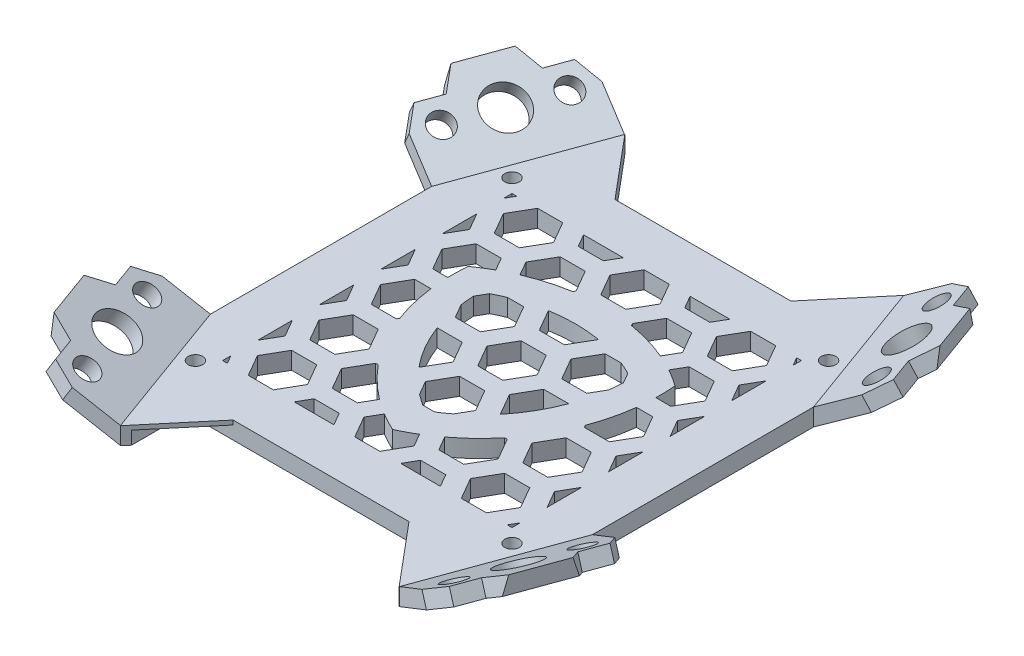
SolidWorks part; units mm, degrees
ref_plane "Front Plane" through (0, 0, 0) normal (0, 0, 1) x (1, 0, 0)
ref_plane "Top Plane" through (0, 0, 0) normal (0, 1, 0) x (1, 0, 0)
ref_plane "Right Plane" through (0, 0, 0) normal (1, 0, 0) x (0, 0, -1)
sketch "Sketch11" plane through (0, 0, 0) normal (0, 1, 0) x (1, 0, 0)
  line L0 (-50, -50) -> (-50, 50)
  line L1 (-30.4059, -66) -> (30.4059, -66)
  line L2 (-66, -38.2239) -> (-66, 0)
  line L3 (-30.4059, 66) -> (30.4059, 66)
  line L4 (66, -38.2239) -> (66, 38.2239)
  line L5 (-66, -66) -> (66, 66) construction
  line L6 (-50, 50) -> (66, -66) construction
  line L7 (-50, 50) -> (50, 50)
  line L8 (50, -50) -> (50, 50)
  line L9 (-50, -50) -> (50, -50)
  line L18 (-66, 0) -> (-66, 38.2239) construction
  line L19 (-66, -66) -> (-66, 66) construction
  line L20 (66, 38.2239) -> (66, 66) construction
  line L21 (66, -66) -> (66, 66) construction
  line L22 (66, -66) -> (66, -38.2239) construction
  line L23 (-66, -66) -> (-66, -38.2239) construction
  line L24 (-48.1804, 87.1828) -> (-65.9654, 38.3188)
  line L27 (-48.1804, 87.1828) -> (-30.4059, 66)
  line L28 (-66, 38.2239) -> (-66, 66) construction
  line L29 (-66, 66) -> (66, 66) construction
  line L30 (0, -55) -> (0, 55) construction
  line L31 (48.1804, 87.1828) -> (30.4059, 66)
  line L32 (65.9654, 38.3188) -> (66, 38.2239)
  line L33 (48.1804, 87.1828) -> (65.9654, 38.3188)
  line L34 (-55, 0) -> (55, 0) construction
  line L35 (65.9654, -38.3188) -> (66, -38.2239)
  line L36 (48.1804, -87.1828) -> (65.9654, -38.3188)
  line L37 (48.1804, -87.1828) -> (30.4059, -66)
  line L38 (-48.1804, -87.1828) -> (-30.4059, -66)
  line L39 (-65.9654, -38.3188) -> (-66, -38.2239)
  line L40 (-48.1804, -87.1828) -> (-65.9654, -38.3188)
  line L41 (30.4059, 66) -> (66, 66) construction
  line L42 (30.4059, -66) -> (66, -66) construction
  line L43 (-66, -66) -> (66, -66) construction
  line L44 (-66, -66) -> (-30.4059, -66) construction
  line L45 (-66, 66) -> (-30.4059, 66) construction
  line L46 (-57.0729, 62.7508) -> (-66, 66) construction
  line L47 (-66, 38.2239) -> (-66, 0)
  line L48 (-66, 38.2239) -> (-65.9654, 38.3188)
  point P0 (0, 0)
  dimension "D1" = 132
  dimension "D2" = 9.5
  dimension "D4" = 52
  dimension "D5" = 60
  dimension "D8" = 20
  dimension "D3" = 16
extrude "Boss-Extrude6" add sketch "Sketch11" along normal blind 6
ref_plane "Plane1" through (4.5644, 0, -12.5405) normal (0.342, 0, -0.9397) x (0, -1, 0)
sketch "Sketch12" plane through (4.5644, 0, -12.5405) normal (0.342, 0, -0.9397) x (0, -1, 0)
  line L0 (-6, 75.093) -> (-21, 101.0738)
  line L1 (-21, 101.0738) -> (-15, 101.0738)
  line L2 (-15, 101.0738) -> (0, 75.093)
  line L4 (-6, 75.093) -> (0, 75.093)
  dimension "D1" = 6
  dimension "D2" = 30
  dimension "D3" = 60
extrude "Boss-Extrude7" add sketch "Sketch12" along normal blind 52
sketch "Sketch13" plane through (-15.1997, -28.0162, -5.5322) normal (0.4698, 0.866, 0.171) x (0.8827, -0.4609, -0.091)
  line L0 (-51.2289, 92.4122) -> (-71.3763, 44.4738) construction
  line L1 (-65.0573, 98.2239) -> (-37.4005, 86.6004) construction
  line L2 (-85.2046, 50.2856) -> (-57.5479, 38.6621) construction
  line L3 (-65.0573, 98.2239) -> (-85.2046, 50.2856) construction
  line L5 (-71.7755, 82.2385) -> (-85.1655, 50.3787) construction
  line L6 (-78.4863, 66.2709) -> (-73.2618, 59.3889)
  line L15 (-73.2618, 59.3889) -> (-76.6247, 51.3873)
  line L16 (-76.6247, 51.3873) -> (-71.3763, 44.4738)
  line L17 (-51.2289, 92.4122) -> (-59.8399, 91.3237)
  line L24 (-71.7755, 82.2385) -> (-63.2027, 83.3222)
  line L25 (-63.2027, 83.3222) -> (-59.8399, 91.3237)
  line L37 (-71.3763, 44.4738) -> (-85.2046, 50.2856)
  line L38 (-85.2046, 50.2856) -> (-78.4863, 66.2709)
  line L39 (-71.7755, 82.2385) -> (-65.0573, 98.2239)
  line L40 (-65.0573, 98.2239) -> (-51.2289, 92.4122)
  line L41 (-85.1655, 50.3787) -> (-78.4863, 66.2709) construction
  line L49 (-44.1188, 70.6151) -> (-49.3553, 77.5128) [skipped]
  line L51 (-60.0486, 83.7209) -> (-71.7755, 82.2385) [skipped]
  line L52 (-81.8532, 58.3033) -> (-86.159, 57.7591) construction
  line L53 (-54.1654, 46.6668) -> (-56.7896, 50.1235) construction
  line L54 (-62.7648, 45.5623) -> (-61.0832, 49.5633) [skipped]
  line L55 (-71.3763, 44.4738) -> (-62.7648, 45.5623) [skipped]
  line L56 (-68.0134, 52.4754) -> (-62.5566, 53.1651) construction
  line L57 (-50.8296, 54.6474) -> (-44.1188, 70.6151) [skipped]
  circle A0 centre (-68.0132, 52.4758) radius 4
  circle A1 centre (-61.3026, 68.443) radius 7
  circle A2 centre (-54.592, 84.4101) radius 4
  dimension "D1" = 8
  dimension "D2" = 8
  dimension "D3" = 14
  dimension "D6" = 17.3397
  dimension "D4" = 17.32
  dimension "D5" = 17.32
  dimension "D7" = 17.3397
  dimension "D8" = 120
  dimension "D9" = 30
  dimension "D10" = 7.4833
  dimension "D11" = 30
extrude "Cut-Extrude1" cut sketch "Sketch13" against normal through all
mirror "Mirror3" about plane through (0, 0, 0) normal (1, 0, 0) of "Cut-Extrude1", "Boss-Extrude7"
mirror "Mirror4" about plane through (0, 0, 0) normal (0, 0, 1) of "Boss-Extrude7", "Cut-Extrude1", "Mirror3"
sketch "Sketch18" plane through (0, 0, 66) normal (0, 0, 1) x (1, 0, 0)
  line L0 (0, 6) -> (0, 0) construction
  line L1 (-30.4059, 6) -> (30.4059, 6) construction
  line L2 (-30.4059, 0) -> (30.4059, 0) construction
  line L3 (0, 4.5) -> (-46.4059, 4.5)
  line L4 (-46.4059, 4.5) -> (-46.4059, 0)
  line L6 (-46.4059, 0) -> (46.4059, 0)
  line L7 (30.4059, 0) -> (48.1804, 0) construction
  line L8 (46.4059, 0) -> (46.4059, 4.5)
  line L9 (46.4059, 4.5) -> (0, 4.5)
  line L11 (-30.4059, 6) -> (-30.4059, 0) construction
  line L12 (30.4059, 6) -> (30.4059, 0) construction
  line L13 (-48.1804, 0) -> (-30.4059, 0) construction
  dimension "D1" = 16
  dimension "D2" = 16
  dimension "D3" = 1.5
extrude "Cut-Extrude2" cut sketch "Sketch18" along normal through all
sketch "Sketch19" plane through (0, 6, 0) normal (0, 1, 0) x (1, 0, 0)
  line L0 (30.4059, 66) -> (-30.4059, 66) construction
  line L3 (-66, 38.2239) -> (-66, -38.2239) construction
  line L4 (66, -38.2239) -> (66, 38.2239) construction
  circle A0 centre (-54.7, 54.7) radius 2.5
  circle A1 centre (54.7, 54.7) radius 2.5
  circle A2 centre (54.7, -54.7) radius 2.5
  circle A3 centre (-54.7, -54.7) radius 2.5
  point P15 (0, 0)
  dimension "D1" = 5
  dimension "D2" = 11.3
  dimension "D3" = 11.3
  dimension "D5" = 11.3
  dimension "D6" = 11.3
  dimension "D4" = 4
extrude "Cut-Extrude3" cut sketch "Sketch19" against normal through all
sketch "Sketch20" plane through (0, 0, 0) normal (0, 1, 0) x (1, 0, 0)
  line L0 (0, 0) -> (0, -28.75) construction
  line L1 (0, 0) -> (-25.9808, 15) construction
  line L2 (0, 0) -> (24.8982, 14.375) construction
  line L3 (8.6603, 21.25) -> (4.3301, 28.75) construction
  line L4 (8.6603, 0) -> (4.3301, 7.5)
  line L5 (4.3301, 7.5) -> (-4.3301, 7.5)
  line L6 (-4.3301, 7.5) -> (-8.6603, 0)
  line L7 (-8.6603, 0) -> (-4.3301, -7.5)
  line L8 (-4.3301, -7.5) -> (4.3301, -7.5)
  line L9 (4.3301, -7.5) -> (8.6603, 0)
  line L10 (4.3301, 28.75) -> (-4.3301, 28.75) construction
  line L11 (-4.3301, 28.75) -> (-8.6603, 21.25) construction
  line L12 (-8.6522, 21.2361) -> (-4.3301, 13.75)
  line L13 (-4.3301, 13.75) -> (4.3301, 13.75)
  line L14 (4.3301, 13.75) -> (8.6522, 21.2361)
  line L15 (8.6603, 42.5) -> (4.3301, 50)
  line L16 (4.3301, 50) -> (-4.3301, 50)
  line L17 (-4.3301, 50) -> (-8.6603, 42.5)
  line L18 (-8.6603, 42.5) -> (-4.3301, 35)
  line L19 (-4.3301, 35) -> (4.3301, 35)
  line L20 (4.3301, 35) -> (8.6603, 42.5)
  line L21 (-11.55, 0) -> (11.55, 0) construction
  line L22 (4.3301, -13.75) -> (8.6603, -21.25)
  line L23 (-4.3301, -13.75) -> (4.3301, -13.75)
  line L24 (-8.6603, -21.25) -> (-4.3301, -13.75)
  line L25 (-5.899, -26.0327) -> (-8.6603, -21.25)
  line L26 (2.0538, -28.75) -> (-2.0538, -28.75)
  line L27 (8.6603, -21.25) -> (5.899, -26.0327)
  line L28 (6.0762, -38.0243) -> (8.6603, -42.5)
  line L29 (-4.3301, -35) -> (4.3301, -35) construction
  line L30 (-8.6603, -42.5) -> (-6.0762, -38.0243)
  line L31 (-4.3301, -50) -> (-8.6603, -42.5)
  line L32 (4.3301, -50) -> (-4.3301, -50)
  line L33 (8.6603, -42.5) -> (4.3301, -50)
  line L34 (4.3301, -7.5) -> (4.3301, -13.75) construction
  line L35 (4.3301, -10.625) -> (18.403, -10.625) construction
  line L36 (11.2674, -34.5157) -> (14.0729, -39.375)
  line L37 (9.7428, -10.625) -> (14.0649, -18.1111)
  line L38 (18.403, -18.125) -> (22.7332, -18.125) construction
  line L39 (22.7332, -18.125) -> (24.8982, -14.375) construction
  line L40 (24.8982, -6.875) -> (22.7332, -3.125) construction
  line L41 (22.7171, -3.125) -> (14.0729, -3.125)
  line L42 (14.0729, -3.125) -> (9.7428, -10.625)
  line L43 (14.0729, -39.375) -> (22.7332, -39.375)
  line L44 (22.7332, -39.375) -> (27.0633, -31.875)
  line L45 (27.0633, -31.875) -> (22.7332, -24.375)
  line L46 (22.7332, -24.375) -> (21.8611, -24.375)
  line L47 (14.0729, -24.375) -> (9.7428, -31.875) construction
  line L48 (9.7428, -53.125) -> (14.0729, -60.625) construction
  line L49 (14.0729, -60.625) -> (22.7332, -60.625) construction
  line L50 (22.7332, -60.625) -> (27.0633, -53.125) construction
  line L51 (25.2591, -50) -> (22.7332, -45.625)
  line L52 (22.7332, -45.625) -> (14.0729, -45.625)
  line L53 (14.0729, -45.625) -> (11.547, -50)
  line L54 (14.0729, 45.625) -> (11.547, 50)
  line L55 (22.7332, 45.625) -> (14.0729, 45.625)
  line L56 (25.2591, 50) -> (22.7332, 45.625)
  line L57 (22.7332, 60.625) -> (27.0633, 53.125) construction
  line L58 (14.0729, 60.625) -> (22.7332, 60.625) construction
  line L59 (9.7428, 53.125) -> (14.0729, 60.625) construction
  line L60 (10.1788, 31.1197) -> (9.7428, 31.875)
  line L61 (22.7332, 24.375) -> (14.0729, 24.375) construction
  line L62 (27.0633, 31.875) -> (24.2578, 27.0157)
  line L63 (22.7332, 39.375) -> (27.0633, 31.875)
  line L64 (14.0729, 39.375) -> (22.7332, 39.375)
  line L65 (9.7428, 31.875) -> (14.0729, 39.375)
  line L66 (14.0729, 3.125) -> (9.7428, 10.625)
  line L67 (22.7332, 3.125) -> (14.0729, 3.125)
  line L68 (25.4945, 7.9077) -> (22.7332, 3.125)
  line L69 (23.8713, 16.1537) -> (25.9251, 12.5963)
  line L70 (14.0729, 18.125) -> (19.5955, 18.125)
  line L71 (9.7428, 10.625) -> (14.0729, 18.125)
  line L72 (45.4663, 42.5) -> (41.1362, 50)
  line L73 (41.1362, 50) -> (32.476, 50)
  line L74 (32.476, 50) -> (28.1458, 42.5)
  line L75 (28.1458, 42.5) -> (32.476, 35)
  line L76 (32.476, 35) -> (41.1362, 35)
  line L77 (41.1362, 35) -> (45.4663, 42.5)
  line L78 (50, 47.1475) -> (48.3531, 50)
  line L79 (46.5489, 53.125) -> (50.879, 60.625) construction
  line L80 (50.879, 60.625) -> (59.5392, 60.625) construction
  line L81 (59.5392, 60.625) -> (63.8694, 53.125) construction
  line L82 (63.8694, 53.125) -> (59.5392, 45.625) construction
  line L83 (59.5392, 45.625) -> (50.879, 45.625) construction
  line L84 (50, 25.8975) -> (46.5489, 31.875)
  line L85 (46.5489, 31.875) -> (50, 37.8525)
  line L86 (50.879, 39.375) -> (59.5392, 39.375) construction
  line L87 (59.5392, 39.375) -> (63.8694, 31.875) construction
  line L88 (63.8694, 31.875) -> (59.5392, 24.375) construction
  line L89 (59.5392, 24.375) -> (50.879, 24.375) construction
  line L90 (45.4663, 21.25) -> (41.1362, 28.75)
  line L91 (41.1362, 28.75) -> (32.476, 28.75)
  line L92 (32.476, 28.75) -> (29.8919, 24.2743)
  line L93 (28.1458, 21.25) -> (32.476, 13.75) construction
  line L94 (35.9682, 13.75) -> (41.1362, 13.75)
  line L95 (41.1362, 13.75) -> (45.4663, 21.25)
  line L96 (50, 4.6475) -> (46.5489, 10.625)
  line L97 (46.5489, 10.625) -> (50, 16.6025)
  line L98 (50.879, 18.125) -> (59.5392, 18.125) construction
  line L99 (59.5392, 18.125) -> (63.8694, 10.625) construction
  line L100 (63.8694, 10.625) -> (59.5392, 3.125) construction
  line L101 (59.5392, 3.125) -> (50.879, 3.125) construction
  line L102 (45.4663, 0) -> (41.1362, 7.5)
  line L103 (41.1362, 7.5) -> (35.5252, 7.5)
  line L104 (32.476, 7.5) -> (28.1458, 0) construction
  line L105 (32.0399, -6.7447) -> (32.476, -7.5)
  line L106 (32.476, -7.5) -> (41.1362, -7.5)
  line L107 (41.1362, -7.5) -> (45.4663, 0)
  line L108 (41.1362, -13.75) -> (45.4663, -21.25)
  line L109 (45.4663, -21.25) -> (41.1362, -28.75)
  line L110 (41.1362, -28.75) -> (32.476, -28.75)
  line L111 (32.476, -28.75) -> (28.1458, -21.25)
  line L112 (28.1458, -21.25) -> (32.476, -13.75)
  line L113 (32.476, -13.75) -> (41.1362, -13.75)
  line L114 (46.5489, -10.625) -> (50, -16.6025)
  line L115 (50.879, -18.125) -> (59.5392, -18.125) construction
  line L116 (59.5392, -18.125) -> (63.8694, -10.625) construction
  line L117 (63.8694, -10.625) -> (59.5392, -3.125) construction
  line L118 (59.5392, -3.125) -> (50.879, -3.125) construction
  line L119 (50, -4.6475) -> (46.5489, -10.625)
  line L120 (46.5489, -31.875) -> (50, -37.8525)
  line L121 (50.879, -39.375) -> (59.5392, -39.375) construction
  line L122 (59.5392, -39.375) -> (63.8694, -31.875) construction
  line L123 (63.8694, -31.875) -> (59.5392, -24.375) construction
  line L124 (59.5392, -24.375) -> (50.879, -24.375) construction
  line L125 (50, -25.8975) -> (46.5489, -31.875)
  line L126 (41.1362, -35) -> (45.4663, -42.5)
  line L127 (45.4663, -42.5) -> (41.1362, -50)
  line L128 (41.1362, -50) -> (32.476, -50)
  line L129 (32.476, -50) -> (28.1458, -42.5)
  line L130 (28.1458, -42.5) -> (32.476, -35)
  line L131 (32.476, -35) -> (41.1362, -35)
  line L132 (46.5489, -53.125) -> (50.879, -60.625) construction
  line L133 (50.879, -60.625) -> (59.5392, -60.625) construction
  line L134 (59.5392, -60.625) -> (63.8694, -53.125) construction
  line L135 (63.8694, -53.125) -> (59.5392, -45.625) construction
  line L136 (59.5392, -45.625) -> (50.879, -45.625) construction
  line L137 (50, -47.1475) -> (48.3531, -50)
  line L138 (0, -11.55) -> (0, 11.55) construction
  line L139 (-50, -47.1475) -> (-48.3531, -50)
  line L140 (-59.5392, -45.625) -> (-50.879, -45.625) construction
  line L141 (-63.8694, -53.125) -> (-59.5392, -45.625) construction
  line L142 (-59.5392, -60.625) -> (-63.8694, -53.125) construction
  line L143 (-50.879, -60.625) -> (-59.5392, -60.625) construction
  line L144 (-46.5489, -53.125) -> (-50.879, -60.625) construction
  line L145 (-50, -25.8975) -> (-46.5489, -31.875)
  line L146 (-59.5392, -24.375) -> (-50.879, -24.375) construction
  line L147 (-63.8694, -31.875) -> (-59.5392, -24.375) construction
  line L148 (-59.5392, -39.375) -> (-63.8694, -31.875) construction
  line L149 (-50.879, -39.375) -> (-59.5392, -39.375) construction
  line L150 (-46.5489, -31.875) -> (-50, -37.8525)
  line L151 (-50, -4.6475) -> (-46.5489, -10.625)
  line L152 (-59.5392, -3.125) -> (-50.879, -3.125) construction
  line L153 (-63.8694, -10.625) -> (-59.5392, -3.125) construction
  line L154 (-59.5392, -18.125) -> (-63.8694, -10.625) construction
  line L155 (-50.879, -18.125) -> (-59.5392, -18.125) construction
  line L156 (-46.5489, -10.625) -> (-50, -16.6025)
  line L157 (-59.5392, 3.125) -> (-50.879, 3.125) construction
  line L158 (-63.8694, 10.625) -> (-59.5392, 3.125) construction
  line L159 (-59.5392, 18.125) -> (-63.8694, 10.625) construction
  line L160 (-50.879, 18.125) -> (-59.5392, 18.125) construction
  line L161 (-46.5489, 10.625) -> (-50, 16.6025)
  line L162 (-50, 4.6475) -> (-46.5489, 10.625)
  line L163 (-59.5392, 24.375) -> (-50.879, 24.375) construction
  line L164 (-63.8694, 31.875) -> (-59.5392, 24.375) construction
  line L165 (-59.5392, 39.375) -> (-63.8694, 31.875) construction
  line L166 (-50.879, 39.375) -> (-59.5392, 39.375) construction
  line L167 (-46.5489, 31.875) -> (-50, 37.8525)
  line L168 (-50, 25.8975) -> (-46.5489, 31.875)
  line L169 (-59.5392, 45.625) -> (-50.879, 45.625) construction
  line L170 (-63.8694, 53.125) -> (-59.5392, 45.625) construction
  line L171 (-59.5392, 60.625) -> (-63.8694, 53.125) construction
  line L172 (-50.879, 60.625) -> (-59.5392, 60.625) construction
  line L173 (-46.5489, 53.125) -> (-50.879, 60.625) construction
  line L174 (-50, 47.1475) -> (-48.3531, 50)
  line L175 (-41.1362, 35) -> (-45.4663, 42.5)
  line L176 (-32.476, 35) -> (-41.1362, 35)
  line L177 (-28.1458, 42.5) -> (-32.476, 35)
  line L178 (-32.476, 50) -> (-28.1458, 42.5)
  line L179 (-41.1362, 50) -> (-32.476, 50)
  line L180 (-45.4663, 42.5) -> (-41.1362, 50)
  line L181 (-41.1362, 13.75) -> (-45.4663, 21.25)
  line L182 (-35.9682, 13.75) -> (-41.1362, 13.75)
  line L183 (-28.1458, 21.25) -> (-32.476, 13.75) construction
  line L184 (-32.476, 28.75) -> (-29.8919, 24.2743)
  line L185 (-41.1362, 28.75) -> (-32.476, 28.75)
  line L186 (-45.4663, 21.25) -> (-41.1362, 28.75)
  line L187 (-41.1362, -7.5) -> (-45.4663, 0)
  line L188 (-32.476, -7.5) -> (-41.1362, -7.5)
  line L189 (-32.0399, -6.7447) -> (-32.476, -7.5)
  line L190 (-32.476, 7.5) -> (-28.1458, 0) construction
  line L191 (-41.1362, 7.5) -> (-35.5252, 7.5)
  line L192 (-45.4663, 0) -> (-41.1362, 7.5)
  line L193 (-32.476, -13.75) -> (-41.1362, -13.75)
  line L194 (-28.1458, -21.25) -> (-32.476, -13.75)
  line L195 (-32.476, -28.75) -> (-28.1458, -21.25)
  line L196 (-41.1362, -28.75) -> (-32.476, -28.75)
  line L197 (-45.4663, -21.25) -> (-41.1362, -28.75)
  line L198 (-41.1362, -13.75) -> (-45.4663, -21.25)
  line L199 (-32.476, -35) -> (-41.1362, -35)
  line L200 (-28.1458, -42.5) -> (-32.476, -35)
  line L201 (-32.476, -50) -> (-28.1458, -42.5)
  line L202 (-41.1362, -50) -> (-32.476, -50) construction
  line L203 (-45.4663, -42.5) -> (-41.1362, -50)
  line L204 (-41.1362, -35) -> (-45.4663, -42.5)
  line L205 (-14.0729, -45.625) -> (-11.547, -50)
  line L206 (-22.7332, -45.625) -> (-14.0729, -45.625)
  line L207 (-25.2591, -50) -> (-22.7332, -45.625)
  line L208 (-22.7332, -60.625) -> (-27.0633, -53.125) construction
  line L209 (-14.0729, -60.625) -> (-22.7332, -60.625) construction
  line L210 (-9.7428, -53.125) -> (-14.0729, -60.625) construction
  line L211 (-14.0729, -24.375) -> (-9.7428, -31.875) construction
  line L212 (-22.7332, -24.375) -> (-21.8611, -24.375)
  line L213 (-27.0633, -31.875) -> (-22.7332, -24.375)
  line L214 (-22.7332, -39.375) -> (-27.0633, -31.875)
  line L215 (-14.0729, -39.375) -> (-22.7332, -39.375)
  line L216 (-11.2674, -34.5157) -> (-14.0729, -39.375)
  line L217 (-14.0729, -3.125) -> (-9.7428, -10.625)
  line L218 (-22.7171, -3.125) -> (-14.0729, -3.125)
  line L219 (-27.0633, -10.625) -> (-22.7332, -3.125) construction
  line L220 (-22.7332, -18.125) -> (-27.0633, -10.625) construction
  line L221 (-14.0729, -18.125) -> (-22.7332, -18.125) construction
  line L222 (-9.7428, -10.625) -> (-14.0649, -18.1111)
  line L223 (-22.7332, 3.125) -> (-14.0729, 3.125)
  line L224 (-25.4945, 7.9077) -> (-22.7332, 3.125)
  line L225 (-23.8713, 16.1537) -> (-25.9251, 12.5963)
  line L226 (-14.0729, 18.125) -> (-19.5955, 18.125)
  line L227 (-9.7428, 10.625) -> (-14.0729, 18.125)
  line L228 (-14.0729, 3.125) -> (-9.7428, 10.625)
  line L229 (-22.7332, 24.375) -> (-14.0729, 24.375) construction
  line L230 (-27.0633, 31.875) -> (-24.2578, 27.0157)
  line L231 (-22.7332, 39.375) -> (-27.0633, 31.875)
  line L232 (-14.0729, 39.375) -> (-22.7332, 39.375)
  line L233 (-9.7428, 31.875) -> (-14.0729, 39.375)
  line L234 (-10.1788, 31.1197) -> (-9.7428, 31.875)
  line L235 (-22.7332, 45.625) -> (-14.0729, 45.625)
  line L236 (-25.2591, 50) -> (-22.7332, 45.625)
  line L237 (-22.7332, 60.625) -> (-27.0633, 53.125) construction
  line L238 (-14.0729, 60.625) -> (-22.7332, 60.625) construction
  line L239 (-9.7428, 53.125) -> (-14.0729, 60.625) construction
  line L240 (-14.0729, 45.625) -> (-11.547, 50)
  line L241 (-48.3531, 50) -> (-46.5489, 53.125) construction
  line L242 (-48.3531, 50) -> (-25.2591, 50)
  line L243 (-50, 47.1475) -> (-50, 37.8525)
  line L244 (-48.3531, -50) -> (-25.2591, -50) construction
  line L245 (50, 47.1475) -> (50, 37.8525)
  line L246 (-50.879, 45.625) -> (-50, 47.1475) construction
  line L247 (-50, 50) -> (-50, 47.1475) construction
  line L248 (-50, 50) -> (-48.3531, 50) construction
  line L249 (-50, 37.8525) -> (-50.879, 39.375) construction
  line L250 (-50.879, 24.375) -> (-50, 25.8975) construction
  line L251 (-50, 16.6025) -> (-50.879, 18.125) construction
  line L252 (-50.879, 3.125) -> (-50, 4.6475) construction
  line L253 (-50.879, -3.125) -> (-50, -4.6475) construction
  line L254 (-50, -16.6025) -> (-50.879, -18.125) construction
  line L255 (-50, 37.8525) -> (-50, 25.8975) construction
  line L256 (-50, 25.8975) -> (-50, 16.6025)
  line L257 (-50, 16.6025) -> (-50, 4.6475) construction
  line L258 (-50, 4.6475) -> (-50, -4.6475)
  line L259 (-50, -4.6475) -> (-50, -16.6025) construction
  line L260 (-50, -16.6025) -> (-50, -25.8975)
  line L261 (-50, -25.8975) -> (-50, -37.8525) construction
  line L262 (-50, -37.8525) -> (-50, -47.1475)
  line L263 (-50.879, -24.375) -> (-50, -25.8975) construction
  line L264 (-50, -37.8525) -> (-50.879, -39.375) construction
  line L265 (-50.879, -45.625) -> (-50, -47.1475) construction
  line L266 (-48.3531, -50) -> (-46.5489, -53.125) construction
  line L267 (-50, -50) -> (-48.3531, -50) construction
  line L268 (-50, -47.1475) -> (-50, -50) construction
  line L269 (-27.0633, -53.125) -> (-25.2591, -50) construction
  line L270 (-11.547, -50) -> (-9.7428, -53.125) construction
  line L271 (11.547, -50) -> (9.7428, -53.125) construction
  line L272 (27.0633, -53.125) -> (25.2591, -50) construction
  line L273 (11.547, -50) -> (25.2591, -50) construction
  line L274 (25.2591, -50) -> (48.3531, -50)
  line L275 (-25.2591, -50) -> (-11.547, -50) construction
  line L276 (-11.547, -50) -> (11.547, -50)
  line L277 (48.3531, -50) -> (46.5489, -53.125) construction
  line L278 (50.879, -45.625) -> (50, -47.1475) construction
  line L279 (50, -47.1475) -> (50, -50) construction
  line L280 (48.3531, -50) -> (50, -50) construction
  line L281 (50.879, -24.375) -> (50, -25.8975) construction
  line L282 (50, -37.8525) -> (50.879, -39.375) construction
  line L283 (50, -25.8975) -> (50, -37.8525) construction
  line L284 (50, -37.8525) -> (50, -47.1475)
  line L285 (50.879, -3.125) -> (50, -4.6475) construction
  line L286 (50, -16.6025) -> (50.879, -18.125) construction
  line L287 (50, -4.6475) -> (50, -16.6025) construction
  line L288 (50, -16.6025) -> (50, -25.8975)
  line L289 (50, 16.6025) -> (50.879, 18.125) construction
  line L290 (50.879, 3.125) -> (50, 4.6475) construction
  line L291 (50, 16.6025) -> (50, 4.6475) construction
  line L292 (50, 4.6475) -> (50, -4.6475)
  line L293 (50, 37.8525) -> (50.879, 39.375) construction
  line L294 (50.879, 24.375) -> (50, 25.8975) construction
  line L295 (50, 37.8525) -> (50, 25.8975) construction
  line L296 (50, 25.8975) -> (50, 16.6025)
  line L297 (50.879, 45.625) -> (50, 47.1475) construction
  line L298 (48.3531, 50) -> (46.5489, 53.125) construction
  line L299 (48.3531, 50) -> (50, 50) construction
  line L300 (50, 50) -> (50, 47.1475) construction
  line L301 (11.547, 50) -> (9.7428, 53.125) construction
  line L302 (27.0633, 53.125) -> (25.2591, 50) construction
  line L303 (11.547, 50) -> (25.2591, 50) construction
  line L304 (25.2591, 50) -> (48.3531, 50)
  line L305 (-11.547, 50) -> (-9.7428, 53.125) construction
  line L306 (-27.0633, 53.125) -> (-25.2591, 50) construction
  line L307 (-25.2591, 50) -> (-11.547, 50) construction
  line L308 (-11.547, 50) -> (11.547, 50)
  line L309 (-14.0729, 24.375) -> (-10.1788, 31.1197) construction
  line L310 (-24.2578, 27.0157) -> (-22.7332, 24.375) construction
  line L311 (14.0729, 24.375) -> (10.1788, 31.1197) construction
  line L312 (24.2578, 27.0157) -> (22.7332, 24.375) construction
  line L313 (29.8919, 24.2743) -> (28.1458, 21.25) construction
  line L314 (32.476, 13.75) -> (35.9682, 13.75) construction
  line L315 (35.5252, 7.5) -> (32.476, 7.5) construction
  line L316 (28.1458, 0) -> (32.0399, -6.7447) construction
  line L317 (21.8611, -24.375) -> (14.0729, -24.375) construction
  line L318 (9.7428, -31.875) -> (11.2674, -34.5157) construction
  line L319 (-6.0762, -38.0243) -> (-4.3301, -35) construction
  line L320 (4.3301, -35) -> (6.0762, -38.0243) construction
  line L321 (-21.8611, -24.375) -> (-14.0729, -24.375) construction
  line L322 (-9.7428, -31.875) -> (-11.2674, -34.5157) construction
  line L323 (-28.1458, 0) -> (-32.0399, -6.7447) construction
  line L324 (-35.5252, 7.5) -> (-32.476, 7.5) construction
  line L325 (-32.476, 13.75) -> (-35.9682, 13.75) construction
  line L326 (-29.8919, 24.2743) -> (-28.1458, 21.25) construction
  line L327 (-22.7332, 18.125) -> (-23.8713, 16.1537) construction
  line L328 (-19.5955, 18.125) -> (-22.7332, 18.125) construction
  line L329 (-25.9251, 12.5963) -> (-27.0633, 10.625) construction
  line L330 (-27.0633, 10.625) -> (-25.4945, 7.9077) construction
  line L331 (-4.3301, -28.75) -> (-5.899, -26.0327) construction
  line L332 (-2.0538, -28.75) -> (-4.3301, -28.75) construction
  line L333 (4.3301, -28.75) -> (2.0538, -28.75) construction
  line L334 (5.899, -26.0327) -> (4.3301, -28.75) construction
  line L335 (0, -28.75) -> (0, -30) construction
  line L336 (14.0729, -18.125) -> (18.403, -18.125) construction
  line L337 (27.0633, -10.625) -> (24.8982, -6.875) construction
  line L338 (24.8982, -14.375) -> (27.0633, -10.625) construction
  line L339 (25.9251, 12.5963) -> (27.0633, 10.625) construction
  line L340 (27.0633, 10.625) -> (25.4945, 7.9077) construction
  line L341 (24.8982, 14.375) -> (25.9808, 15) construction
  line L342 (22.7332, 18.125) -> (23.8713, 16.1537) construction
  line L343 (19.5955, 18.125) -> (22.7332, 18.125) construction
  line L344 (-8.6603, 21.25) -> (-8.6522, 21.2361) construction
  line L345 (8.6522, 21.2361) -> (8.6603, 21.25) construction
  line L346 (22.7332, -3.125) -> (22.7171, -3.125) construction
  line L347 (14.0649, -18.1111) -> (14.0729, -18.125) construction
  line L348 (-14.0649, -18.1111) -> (-14.0729, -18.125) construction
  line L349 (-22.7332, -3.125) -> (-22.7171, -3.125) construction
  line L350 (-41.1362, -50) -> (-48.3531, -50)
  line L351 (-32.476, -50) -> (-25.2591, -50)
  arc A0 (2.0538, -28.75) -> (5.899, -26.0327) centre (-25.9808, 15) ccw
  arc A1 (-25.9251, 12.5963) -> (-25.4945, 7.9077) centre (25.9808, 15) ccw
  arc A2 (23.8713, 16.1537) -> (19.5955, 18.125) centre (0, -30) ccw
  arc A3 (0, -41.2515) -> (6.0762, -38.0243) centre (-25.9808, 15) ccw
  arc A4 (35.7248, 20.6257) -> (29.8919, 24.2743) centre (0, -30) ccw
  arc A5 (-35.7248, 20.6257) -> (-35.9682, 13.75) centre (25.9808, 15) ccw
  circle A6 centre (0, 0) radius 7.5 construction
  arc A7 (18.403, -18.125) -> (24.8982, -14.375) centre (18.403, -10.625) ccw construction
  arc A8 (-24.2578, 27.0157) -> (-29.8919, 24.2743) centre (0, -30) ccw construction
  arc A9 (-29.8919, 24.2743) -> (-35.7248, 20.6257) centre (0, -30) ccw
  arc A10 (35.7248, 20.6257) -> (-35.7248, 20.6257) centre (0, -30) ccw construction
  arc A11 (10.1788, 31.1197) -> (-10.1788, 31.1197) centre (0, -30) ccw construction
  arc A12 (-10.1788, 31.1197) -> (-24.2578, 27.0157) centre (0, -30) ccw
  arc A13 (29.8919, 24.2743) -> (24.2578, 27.0157) centre (0, -30) ccw construction
  arc A14 (24.2578, 27.0157) -> (10.1788, 31.1197) centre (0, -30) ccw
  arc A15 (-8.6522, 21.2361) -> (-19.5955, 18.125) centre (0, -30) ccw construction
  arc A16 (-19.5955, 18.125) -> (-23.8713, 16.1537) centre (0, -30) ccw
  arc A17 (25.9808, 15) -> (-25.9808, 15) centre (0, -30) ccw construction
  arc A18 (19.5955, 18.125) -> (8.6522, 21.2361) centre (0, -30) ccw construction
  arc A19 (8.6522, 21.2361) -> (-8.6522, 21.2361) centre (0, -30) ccw
  arc A20 (35.5252, 7.5) -> (35.9682, 13.75) centre (-25.9808, 15) ccw construction
  arc A21 (35.9682, 13.75) -> (35.7248, 20.6257) centre (-25.9808, 15) ccw
  arc A22 (0, -41.2515) -> (35.7248, 20.6257) centre (-25.9808, 15) ccw construction
  arc A23 (21.8611, -24.375) -> (32.0399, -6.7447) centre (-25.9808, 15) ccw construction
  arc A24 (32.0399, -6.7447) -> (35.5252, 7.5) centre (-25.9808, 15) ccw
  arc A25 (6.0762, -38.0243) -> (11.2674, -34.5157) centre (-25.9808, 15) ccw construction
  arc A26 (11.2674, -34.5157) -> (21.8611, -24.375) centre (-25.9808, 15) ccw
  arc A27 (-11.2674, -34.5157) -> (-6.0762, -38.0243) centre (25.9808, 15) ccw construction
  arc A28 (-6.0762, -38.0243) -> (0, -41.2515) centre (25.9808, 15) ccw
  arc A29 (-35.7248, 20.6257) -> (0, -41.2515) centre (25.9808, 15) ccw construction
  arc A30 (-32.0399, -6.7447) -> (-21.8611, -24.375) centre (25.9808, 15) ccw construction
  arc A31 (-21.8611, -24.375) -> (-11.2674, -34.5157) centre (25.9808, 15) ccw
  arc A32 (-35.9682, 13.75) -> (-35.5252, 7.5) centre (25.9808, 15) ccw construction
  arc A33 (-35.5252, 7.5) -> (-32.0399, -6.7447) centre (25.9808, 15) ccw
  arc A34 (-23.8713, 16.1537) -> (-25.9808, 15) centre (0, -30) ccw construction
  arc A35 (-25.9808, 15) -> (-25.9251, 12.5963) centre (25.9808, 15) ccw construction
  arc A36 (-25.9808, 15) -> (0, -30) centre (25.9808, 15) ccw construction
  arc A37 (-25.4945, 7.9077) -> (-22.7171, -3.125) centre (25.9808, 15) ccw construction
  arc A38 (-22.7171, -3.125) -> (-14.0649, -18.1111) centre (25.9808, 15) ccw
  arc A39 (-14.0649, -18.1111) -> (-5.899, -26.0327) centre (25.9808, 15) ccw construction
  arc A40 (-5.899, -26.0327) -> (-2.0538, -28.75) centre (25.9808, 15) ccw
  arc A41 (-2.0538, -28.75) -> (0, -30) centre (25.9808, 15) ccw construction
  arc A42 (0, -30) -> (2.0538, -28.75) centre (-25.9808, 15) ccw construction
  arc A43 (0, -30) -> (25.9808, 15) centre (-25.9808, 15) ccw construction
  arc A44 (5.899, -26.0327) -> (14.0649, -18.1111) centre (-25.9808, 15) ccw construction
  arc A45 (14.0649, -18.1111) -> (22.7171, -3.125) centre (-25.9808, 15) ccw
  arc A46 (14.7992, -17.2024) -> (18.403, -18.125) centre (18.403, -10.625) ccw construction
  arc A47 (24.8982, -14.375) -> (24.8982, -6.875) centre (18.403, -10.625) ccw construction
  arc A48 (22.2973, -4.2153) -> (14.7992, -17.2024) centre (18.403, -10.625) ccw construction
  arc A49 (22.7171, -3.125) -> (25.4945, 7.9077) centre (-25.9808, 15) ccw construction
  arc A50 (25.4945, 7.9077) -> (25.9251, 12.5963) centre (-25.9808, 15) ccw
  arc A51 (24.8982, -6.875) -> (22.2973, -4.2153) centre (18.403, -10.625) ccw construction
  arc A52 (25.9251, 12.5963) -> (25.9808, 15) centre (-25.9808, 15) ccw construction
  arc A53 (25.9808, 15) -> (23.8713, 16.1537) centre (0, -30) ccw construction
  dimension "D1" = 10
  dimension "D2" = 30
  dimension "D3" = 15
  dimension "D4" = 120
  dimension "D5" = 120
  dimension "D6" = 3
  dimension "D7" = 6.25
  dimension "D8" = 6.25
  dimension "D9" = 15
  dimension "D11" = 6.25
  dimension "D13" = 6.25
  dimension "D10" = 3
  dimension "D12" = 2
extrude "Boss-Extrude9" add sketch "Sketch20" along normal up to surface (6 mm away) contours L351 L207 L206 L205 L276 L53 L52 L51 L274 L137 L284 L120 L125 L288 L114 L119 L292 L96 L97 L296 L84 L85 L245 L78 L304 L56 L55 L54 L308 L240 L235 L236 L242 L174 L243 L167 L168 L256 L161 L162 L258 L151 L156 L260 L145 L150 L262 L139 L350 L203 L204 L199 L200 L201 | L175 L180 L179 L178 L177 L176 | L15 L16 L17 L18 L19 L20 | L60 L65 L64 L63 L62 A14 | L72 L73 L74 L75 L76 L77 | A4 L92 L91 L90 L95 L94 A21 | L13 L14 A19 L12 | L230 A12 L234 L233 L232 L231 | L184 A9 A5 L182 L181 L186 L185 | L189 L188 L187 L192 L191 A33 | L225 A1 L224 L223 L228 L227 L226 A16 | L4 L5 L6 L7 L8 L9 | L69 A50 L68 L67 L66 L71 L70 A2 | L103 A24 L105 L106 L107 L102 | L108 L109 L110 L111 L112 L113 | L37 A45 L41 L42 | L26 A40 L25 L24 L23 L22 L27 A0 | L218 L217 L222 A38 | L193 L198 L197 L196 L195 L194 | L216 L215 L214 L213 L212 A31 | A3 L28 L33 L32 L31 L30 A28 | L46 A26 L36 L43 L44 L45 | L126 L127 L128 L129 L130 L131 up to face at (-54.7, 6, 57.2)
